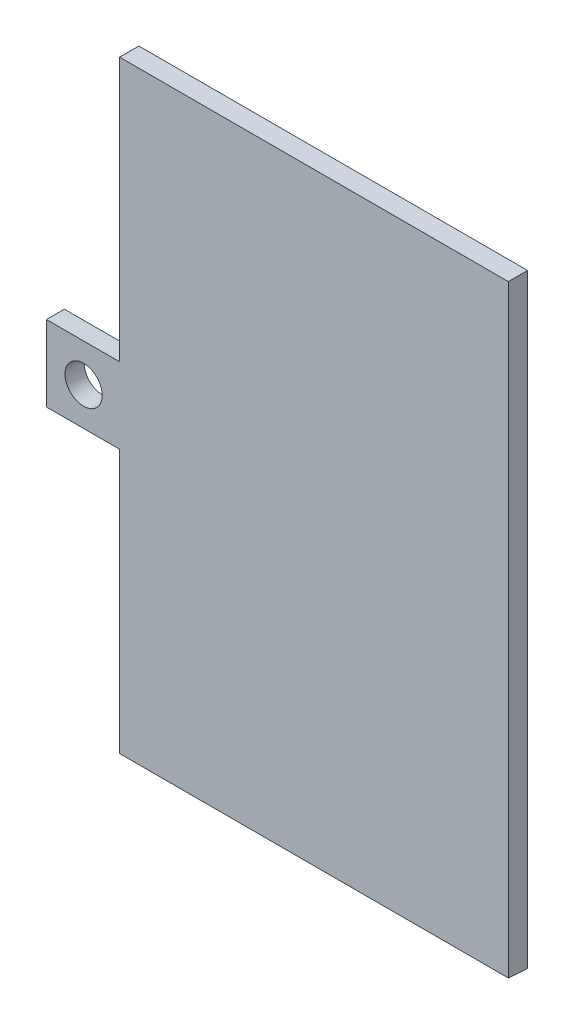
SolidWorks part; units mm, degrees
ref_plane "Front Plane" through (0, 0, 0) normal (0, 0, 1) x (1, 0, 0)
ref_plane "Top Plane" through (0, 0, 0) normal (0, 1, 0) x (1, 0, 0)
ref_plane "Right Plane" through (0, 0, 0) normal (1, 0, 0) x (0, 0, -1)
sketch "Sketch1" plane through (0, 0, 0) normal (0, 0, 1) x (1, 0, 0)
  line L4 (-78.5896, 18.8431) -> (-78.5896, 74.6081)
  line L5 (-111.3547, 18.8431) -> (-78.5896, 18.8431)
  line L6 (-111.3547, 74.6081) -> (-111.3547, 18.8431)
  line L7 (-78.5896, 74.6081) -> (-111.3547, 74.6081)
  line L9 (-123.3547, 77.657) -> (-73.5896, 77.657)
  line L10 (-123.3547, 77.657) -> (-123.3547, 12.727)
  line L11 (-123.3547, 12.727) -> (-73.5896, 12.727)
  line L12 (-73.5896, 77.657) -> (-73.5896, 12.727)
  dimension "D1" = 12
  dimension "D2" = 5
  dimension "D3" = 64.93
  dimension "D4" = 32.7651
  dimension "D5" = 3.0488
  dimension "D6" = 73.5896
  dimension "D7" = 12.727
  dimension "D8" = 55.7651
  dimension "D9" = 49.7651
extrude "Boss-Extrude1" add sketch "Sketch1" along normal blind 2 draft 2 contours L10 L11 L12 L9
sketch "Sketch3" plane through (0, 0, 2) normal (0, 0, 1) x (1, 0, 0)
  line L0 (-123.2849, 77.5871) -> (-73.6595, 77.5871) construction
  line L1 (-123.2849, 77.5871) -> (-123.2849, 12.7968) construction
  circle A0 centre (-119.2849, 45.1771) radius 2
  dimension "D2" = 4
  dimension "D1" = 32.41
  dimension "D3" = 4
extrude "Cut-Extrude2" cut sketch "Sketch3" against normal up to next (2 mm away) draft 2
sketch "Sketch4" plane through (0, 0, 0) normal (0, 0, -1) x (-1, 0, 0)
  line L1 (123.3547, 77.657) -> (115.3547, 77.657)
  line L2 (123.3547, 77.657) -> (123.3547, 49.1771)
  line L3 (123.3547, 49.1771) -> (115.3547, 49.1771)
  line L4 (115.3547, 77.657) -> (115.3547, 49.1771)
  line L5 (123.3547, 12.727) -> (115.3547, 12.727)
  line L6 (123.3547, 12.727) -> (123.3547, 41.1771)
  line L7 (123.3547, 41.1771) -> (115.3547, 41.1771)
  line L8 (115.3547, 12.727) -> (115.3547, 41.1771)
  circle A0 centre (119.2849, 45.1771) radius 1.9302 construction
  dimension "D1" = 4
  dimension "D2" = 4
  dimension "D3" = 8
  dimension "D4" = 8
extrude "Cut-Extrude3" cut sketch "Sketch4" against normal up to next (2 mm away) draft 2
